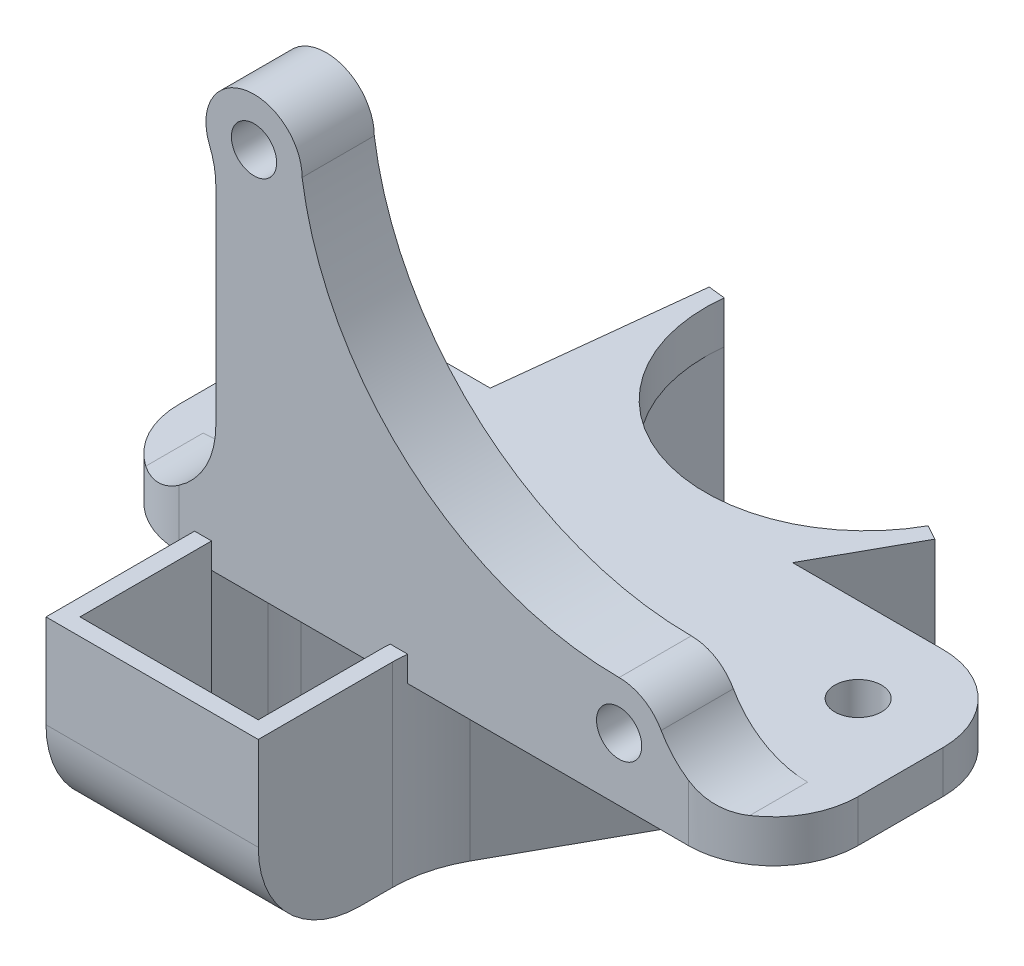
SolidWorks part; units mm, degrees
ref_plane "Front Plane" through (0, 0, 0) normal (0, 0, 1) x (1, 0, 0)
ref_plane "Top Plane" through (0, 0, 0) normal (0, 1, 0) x (1, 0, 0)
ref_plane "Right Plane" through (0, 0, 0) normal (1, 0, 0) x (0, 0, -1)
sketch "Sketch1" plane through (0, 0, 0) normal (0, 1, 0) x (1, 0, 0)
  line L0 (30, 5) -> (40, 5) construction
  line L1 (-40, 15) -> (40, 15)
  line L2 (-40, 15) -> (-40, -15)
  line L3 (-40, -15) -> (40, -15)
  line L4 (40, 15) -> (40, -15)
  line L5 (-40, 15) -> (40, -15) construction
  line L6 (-40, -15) -> (40, 15) construction
  line L7 (30, 5) -> (-30, 5) construction
  line L8 (-30, 5) -> (-40, 5) construction
  circle A0 centre (30, 5) radius 2.75
  circle A1 centre (-30, 5) radius 2.75
  point P0 (0, 0)
  dimension "D2" = 10
  dimension "D3" = 5.5
  dimension "D4" = 20
  dimension "D5" = 10
  dimension "D1" = 60
extrude "Boss-Extrude1" add sketch "Sketch1" along normal blind 5
sketch "Sketch2" plane through (0, 5, 0) normal (0, 1, 0) x (1, 0, 0)
  line L0 (-40, -15) -> (40, -15) construction
  line L1 (-25.65, -15) -> (25.65, -15)
  line L2 (-25.65, -15) -> (-25.65, -6.5)
  line L3 (-25.65, -6.5) -> (25.65, -6.5)
  line L4 (25.65, -15) -> (25.65, -6.5)
  line L5 (-25.65, -15) -> (25.65, -6.5) construction
  line L6 (-25.65, -6.5) -> (25.65, -15) construction
  line L7 (-25.65, -15) -> (-40, -15) construction
  line L8 (25.65, -15) -> (40, -15) construction
  point P4 (0, -10.75)
  dimension "D1" = 8.5
  dimension "D2" = 51.3
extrude "Boss-Extrude2" add sketch "Sketch2" along normal blind 50
sketch "Sketch3" plane through (0, 0, 15) normal (0, 0, 1) x (1, 0, 0)
  line L0 (-25.65, 55) -> (-25.65, 5) construction
  line L1 (-25.65, 55) -> (25.65, 55) construction
  line L2 (-40, 0) -> (40, 0) construction
  line L3 (25.65, 55) -> (25.65, 5) construction
  circle A2 centre (21.85, 7.4) radius 2.665
  circle A3 centre (-21.15, 45.4) radius 2.665
  dimension "D1" = 4.5
  dimension "D2" = 9.6
  dimension "D3" = 7.4
  dimension "D4" = 3.8
  dimension "D5" = 5.33
  dimension "D6" = 5.33
extrude "Cut-Extrude1" cut sketch "Sketch3" against normal blind 8
sketch "Sketch5" plane through (0, 0, 15) normal (0, 0, 1) x (1, 0, 0)
  line L8 (-40, 0) -> (40, 0)
  line L9 (40, 0) -> (40, 5)
  line L10 (40, 5) -> (25.65, 5)
  line L11 (25.65, 5) -> (25.65, 55)
  line L12 (25.65, 55) -> (-25.65, 55)
  line L13 (-25.65, 55) -> (-25.65, 5)
  line L14 (-25.65, 5) -> (-40, 5)
  line L15 (-40, 5) -> (-40, 0)
  line L16 (-40, 0) -> (40, 0)
  line L17 (40, 0) -> (40, 5)
  line L18 (40, 5) -> (25.65, 5)
  line L19 (25.65, 5) -> (25.65, 55)
  line L20 (25.65, 55) -> (-25.65, 55)
  line L21 (-25.65, 55) -> (-25.65, 5)
  line L22 (-25.65, 5) -> (-40, 5)
  line L23 (-40, 5) -> (-40, 0)
  circle A7 centre (-21.15, 45.4) radius 5.665
  circle A8 centre (-21.15, 45.4) radius 5.665
  arc A9 (-15.485, 45.4) -> (21.85, 13.065) centre (21.85, 50.7866) ccw
  circle A10 centre (21.85, 7.4) radius 5.665
  circle A11 centre (21.85, 7.4) radius 5.665
  line M16 (25.65, 5) -> (25.65, 55)
  line M17 (25.65, 55) -> (-25.65, 55)
  line M18 (-25.65, 55) -> (-25.65, 5)
  dimension "D1" = 3
  dimension "D2" = 3
  dimension "D3" = 0
extrude "Cut-Extrude2" cut sketch "Sketch5" against normal up to next contours A11 L19 A8 A9 M17 M18 region at (6.6454, 37.1712, 15)
extrude "Boss-Extrude3" add sketch "Sketch5<3>" against normal up to surface (8.5 mm away) contours L18 A11 M16 | L21 A8 region at (26.4483, 7.8382, 15) region at (-26.1204, 45.4, 15) up to face at (0.2845, 20.991, 6.5)
sketch "Sketch5<3>" plane through (0, 0, 15) normal (0, 0, 1) x (1, 0, 0) same geometry as "Sketch5"
fillet "Fillet1" radius 10 3 edges at (26.9815, 5, 10.75) (-25.65, 5, 10.75) (-25.65, 41.9587, 10.75)
fillet "Fillet2" radius 10 4 edges at (40, 2.5, 15) (40, 2.5, -15) (-40, 2.5, -15) (-40, 2.5, 15)
sketch "Sketch6" plane through (0, 0, 15) normal (0, 0, 1) x (1, 0, 0)
  line L1 (-6.65, 0) -> (-24.65, 0) construction
sketch "Sketch7" plane through (0, 0, 0) normal (0, -1, 0) x (1, 0, 0)
  line L0 (-6.65, 15) -> (-24.65, 15) construction
  line L1 (-6.65, 15) -> (-24.65, 15)
  line L2 (-6.65, 15) -> (-6.65, -35.9) construction
  line L3 (-6.65, -35.9) -> (0, -35.9) construction
  line L4 (-24.65, 15) -> (-18.7594, -37.9855)
  line L5 (-6.65, 15) -> (16.5057, -26.7442)
  line L6 (-4.3629, 15) -> (18.2546, -25.7741)
  line L7 (-26.6378, 14.779) -> (-20.7472, -38.2065)
  line L8 (-26.6378, 14.779) -> (-26.6623, 15)
  line L9 (-30, 15) -> (30, 15) construction
  line L10 (-24.65, 15) -> (-26.6623, 15)
  line L11 (-6.65, 15) -> (-4.3629, 15)
  line L12 (-4.9011, 15.9701) -> (18.2546, -25.7741) construction
  line L13 (-18.7594, -37.9855) -> (-20.7472, -38.2065)
  line L14 (18.2546, -25.7741) -> (16.5057, -26.7442)
  line L15 (-6.65, 15) -> (-4.3629, 15)
  circle A0 centre (0, -35.9) radius 15.875 construction
  arc A1 (16.5057, -26.7442) -> (-18.7594, -37.9855) centre (0, -35.9) ccw
  circle A2 centre (0, -35.9) radius 18.875 construction
  line M5 (30, 15) -> (-30, 15)
  line M9 (-30, -15) -> (30, -15)
  dimension "D3" = 31.75
  dimension "D1" = 6.65
  dimension "D2" = 50.9
  dimension "D4" = 3
  dimension "D5" = 2
  dimension "D6" = 2
extrude "Boss-Extrude5" add sketch "Sketch7" against normal up to surface (5 mm away) contours A1 L5 L4 M9 | L13 L4 L7 M9 | L14 L6 L5 M9 region at (14.2429, 0, -20.6331) region at (12.8614, 0, -21.0868) region at (-21.0387, 0, -26.5481) up to face at (-0.0182, 5, 0.6525)
extrude "Boss-Extrude6" add sketch "Sketch7<6>" along normal blind 20 contours L6 L5 M5 M9 | L14 L6 L5 M9 | L8 L7 L4 M9 M5 | L13 L4 L7 M9 region at (2.8141, 0, 0) region at (-23.9886, 0, 0) region at (14.2429, 0, -20.6331) region at (-21.0387, 0, -26.5481)
sketch "Sketch7<6>" plane through (0, 0, 0) normal (0, -1, 0) x (1, 0, 0) same geometry as "Sketch7"
sketch "Sketch8" plane through (0, 0, 0) normal (0, -1, 0) x (1, 0, 0)
  line L3 (-5.65, 22) -> (-5.65, 30) construction
  line L4 (-25.65, 22) -> (-25.65, 30) construction
  line L5 (-5.65, 30) -> (-25.65, 30) construction
  line L6 (-5.15, 22) -> (-5.15, 30.5)
  line L7 (-5.15, 30.5) -> (-26.15, 30.5)
  line L8 (-26.15, 22) -> (-26.15, 30.5)
  line L9 (-26.15, 22) -> (-26.15, 15)
  line L10 (-24.65, 15) -> (-26.6623, 15) construction
  line L11 (-5.15, 22) -> (-5.15, 15)
  line L12 (-28.15, 22) -> (-28.15, 15)
  line L13 (-28.15, 22) -> (-28.15, 32.5)
  line L14 (-3.15, 32.5) -> (-28.15, 32.5)
  line L15 (-3.15, 22) -> (-3.15, 32.5)
  line L16 (-3.15, 22) -> (-3.15, 15)
  line L17 (-28.15, 15) -> (-25.9441, 8.5399)
  line L18 (-23.3271, -15) -> (-26.6623, 15) construction
  line L19 (-25.9441, 8.5399) -> (-26.6623, 15)
  line L20 (-26.6623, 15) -> (-26.15, 15)
  line L21 (-3.15, 15) -> (-3.15, 12.8134)
  line L22 (-4.3629, 15) -> (12.2782, -15) construction
  line L23 (-3.15, 12.8134) -> (-4.3629, 15)
  line L24 (-4.3629, 15) -> (-5.15, 15)
  line L25 (-26.15, 15) -> (-23.9259, 8.4864)
  line L26 (-24.65, 15) -> (-18.7594, -37.9855) construction
  line L27 (-23.9259, 8.4864) -> (-24.65, 15)
  line L28 (-6.65, 15) -> (-24.65, 15) construction
  line L29 (-24.65, 15) -> (-26.15, 15)
  line L30 (-5.15, 15) -> (-5.15, 12.2959)
  line L31 (-6.65, 15) -> (16.5057, -26.7442) construction
  line L32 (-5.15, 12.2959) -> (-6.65, 15)
  line L33 (-6.65, 15) -> (-5.15, 15)
  line M8 (30, 15) -> (-4.3629, 15)
  line M9 (-4.3629, 15) -> (12.2782, -15)
  dimension "D1" = 0.5
  dimension "D2" = 2
extrude "Boss-Extrude7" add sketch "Sketch8" along normal up to surface (20 mm away) contours L24 L16 L15 L14 L13 L12 L17 L19 L20 L9 L8 L7 L6 L11 M8 | L21 M8 M9 region at (-4.8037, 0, 26.25) region at (-3.5543, 0, 14.2711) up to face at (5.9369, -20, -5.6296)
extrude "Cut-Extrude3" cut sketch "Sketch8<3>" along normal up to surface (20 mm away) contours L27 L29 L25 | L33 L32 L30 region at (-24.9086, 0, 12.8288) region at (-5.65, 0, 14.0986) up to face at (-12.4794, -20, 6.2429)
sketch "Sketch8<3>" plane through (0, 0, 0) normal (0, -1, 0) x (1, 0, 0) same geometry as "Sketch8"
sketch "Sketch9" plane through (0, 0, 0) normal (0, 1, 0) x (1, 0, 0)
  line L8 (-3.15, -32.5) -> (-3.15, -15)
  line L9 (-3.15, -15) -> (-5.15, -15)
  line L10 (-5.15, -15) -> (-5.15, -30.5)
  line L11 (-5.15, -30.5) -> (-26.15, -30.5)
  line L12 (-26.15, -30.5) -> (-26.15, -15)
  line L13 (-26.15, -15) -> (-28.15, -15)
  line L14 (-28.15, -15) -> (-28.15, -32.5)
  line L15 (-28.15, -32.5) -> (-3.15, -32.5)
  line L16 (-3.15, -32.5) -> (-3.15, -15)
  line L17 (-3.15, -15) -> (-5.15, -15)
  line L18 (-5.15, -15) -> (-5.15, -30.5)
  line L19 (-5.15, -30.5) -> (-26.15, -30.5)
  line L20 (-26.15, -30.5) -> (-26.15, -15)
  line L21 (-26.15, -15) -> (-28.15, -15)
  line L22 (-28.15, -15) -> (-28.15, -32.5)
  line L23 (-28.15, -32.5) -> (-3.15, -32.5)
  dimension "D1" = 0
extrude "Boss-Extrude8" add sketch "Sketch9" along normal blind 3
fillet "Fillet4" radius 15 5 edges at (-23.9259, -10, 8.4864) (-25.9441, -10, 8.5399) (-28.15, -10, 15) (-5.15, -10, 12.2959) (-3.15, -10, 12.8134)
sketch "Sketch10" plane through (0, -20, 0) normal (0, -1, 0) x (1, 0, 0)
  line L14 (-5.15, 30.5) -> (-5.15, 16.1775)
  line L15 (-3.2671, 8.9014) -> (16.5057, -26.7442)
  line L16 (16.5057, -26.7442) -> (18.2546, -25.7741)
  line L17 (18.2546, -25.7741) -> (-1.2671, 9.419)
  line L18 (-3.15, 16.6951) -> (-3.15, 32.5)
  line L19 (-3.15, 32.5) -> (-28.15, 32.5)
  line L20 (-28.15, 32.5) -> (-28.15, 17.4904)
  line L21 (-27.3453, 12.6432) -> (-26.4754, 10.0957)
  line L22 (-25.7625, 6.906) -> (-20.7472, -38.2065)
  line L23 (-20.7472, -38.2065) -> (-18.7594, -37.9855)
  line L24 (-18.7594, -37.9855) -> (-23.7442, 6.8525)
  line L25 (-24.4571, 10.0422) -> (-26.15, 15)
  line L26 (-26.15, 15) -> (-26.15, 30.5)
  line L27 (-26.15, 30.5) -> (-5.15, 30.5)
  line L28 (-5.15, 30.5) -> (-5.15, 16.1775)
  line L29 (-3.2671, 8.9014) -> (16.5057, -26.7442)
  line L30 (16.5057, -26.7442) -> (18.2546, -25.7741)
  line L31 (18.2546, -25.7741) -> (-1.2671, 9.419)
  line L32 (-3.15, 16.6951) -> (-3.15, 32.5)
  line L33 (-3.15, 32.5) -> (-28.15, 32.5)
  line L34 (-28.15, 32.5) -> (-28.15, 17.4904)
  line L35 (-27.3453, 12.6432) -> (-26.4754, 10.0957)
  line L36 (-25.7625, 6.906) -> (-20.7472, -38.2065)
  line L37 (-20.7472, -38.2065) -> (-18.7594, -37.9855)
  line L38 (-18.7594, -37.9855) -> (-23.7442, 6.8525)
  line L39 (-24.4571, 10.0422) -> (-26.15, 15)
  line L40 (-26.15, 15) -> (-26.15, 30.5)
  line L41 (-26.15, 30.5) -> (-5.15, 30.5)
  arc A0 (16.5057, -26.7442) -> (-18.7594, -37.9855) centre (0, -35.9) ccw construction
  arc A1 (16.5057, -26.7442) -> (-18.7594, -37.9855) centre (0, -35.9) ccw
  arc A5 (-5.15, 16.1775) -> (-3.2671, 8.9014) centre (9.85, 16.1775) ccw
  arc A6 (-3.15, 16.6951) -> (-1.2671, 9.419) centre (11.85, 16.6951) ccw
  arc A7 (-28.15, 17.4904) -> (-27.3453, 12.6432) centre (-13.15, 17.4904) ccw
  arc A8 (-25.7625, 6.906) -> (-26.4754, 10.0957) centre (-40.6706, 5.2486) ccw
  arc A9 (-23.7442, 6.8525) -> (-24.4571, 10.0422) centre (-38.6524, 5.1951) ccw
  arc A10 (-5.15, 16.1775) -> (-3.2671, 8.9014) centre (9.85, 16.1775) ccw
  arc A11 (-3.15, 16.6951) -> (-1.2671, 9.419) centre (11.85, 16.6951) ccw
  arc A12 (-28.15, 17.4904) -> (-27.3453, 12.6432) centre (-13.15, 17.4904) ccw
  arc A13 (-25.7625, 6.906) -> (-26.4754, 10.0957) centre (-40.6706, 5.2486) ccw
  arc A14 (-23.7442, 6.8525) -> (-24.4571, 10.0422) centre (-38.6524, 5.1951) ccw
  line M20 (-5.15, 30.5) -> (-5.15, 16.1775)
  arc M21 (-5.15, 16.1775) -> (-3.2671, 8.9014) centre (9.85, 16.1775) ccw
  line M22 (-3.2671, 8.9014) -> (16.5057, -26.7442)
  line M23 (16.5057, -26.7442) -> (18.2546, -25.7741)
  line M24 (18.2546, -25.7741) -> (-1.2671, 9.419)
  arc M25 (-1.2671, 9.419) -> (-3.15, 16.6951) centre (11.85, 16.6951) cw
  line M26 (-3.15, 16.6951) -> (-3.15, 32.5)
  line M27 (-3.15, 32.5) -> (-28.15, 32.5)
  line M28 (-28.15, 32.5) -> (-28.15, 17.4904)
  arc M29 (-28.15, 17.4904) -> (-27.3453, 12.6432) centre (-13.15, 17.4904) ccw
  line M30 (-27.3453, 12.6432) -> (-26.4754, 10.0957)
  arc M31 (-26.4754, 10.0957) -> (-25.7625, 6.906) centre (-40.6706, 5.2486) cw
  line M32 (-25.7625, 6.906) -> (-20.7472, -38.2065)
  line M33 (-20.7472, -38.2065) -> (-18.7594, -37.9855)
  line M34 (-18.7594, -37.9855) -> (-23.7442, 6.8525)
  arc M35 (-23.7442, 6.8525) -> (-24.4571, 10.0422) centre (-38.6524, 5.1951) ccw
  line M36 (-24.4571, 10.0422) -> (-26.15, 15)
  line M37 (-26.15, 15) -> (-26.15, 30.5)
  line M38 (-26.15, 30.5) -> (-5.15, 30.5)
  dimension "D1" = 0
extrude "Boss-Extrude9" add sketch "Sketch10" against normal blind 2 contours A1 M22 M21 M20 M38 M37 M36 M35 M34 | M38 M20 M21 M22 M23 M24 M25 M26 M27 M28 M29 M30 M31 M32 M33 M34 M35 M36 M37 region at (-15.65, -20, 31.3457) region at (-11.5254, -20, 2.3505)
fillet "Fillet5" radius 12 2 edges at (-15.65, -20, 32.5) (-15.65, -18, 30.5)
